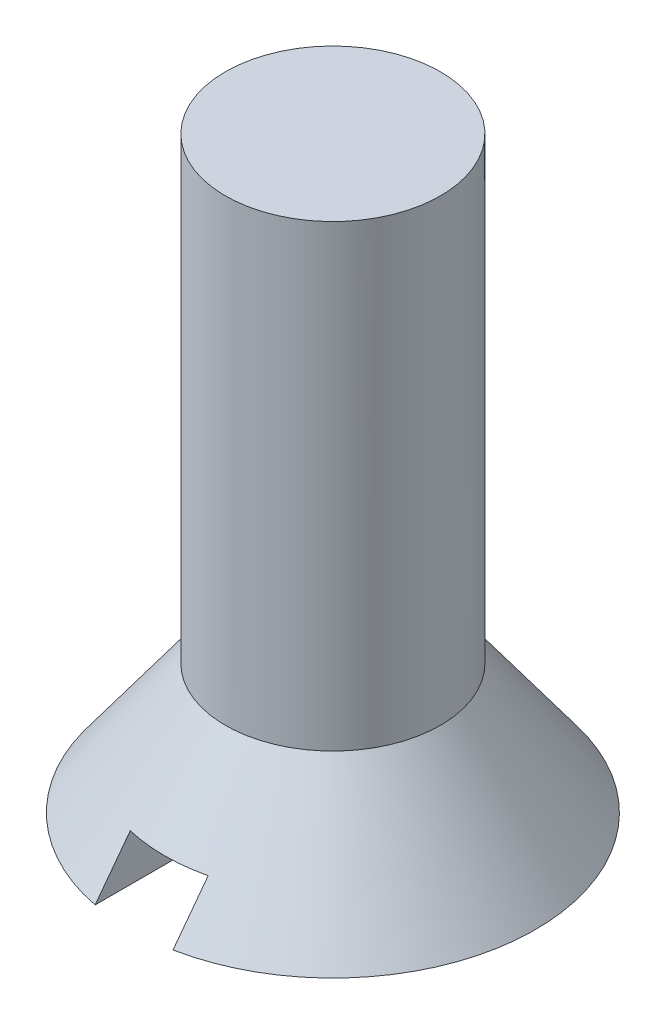
SolidWorks part; units mm, degrees
ref_plane "Front Plane" through (0, 0, 0) normal (0, 0, 1) x (1, 0, 0)
ref_plane "Top Plane" through (0, 0, 0) normal (0, 1, 0) x (1, 0, 0)
ref_plane "Right Plane" through (0, 0, 0) normal (1, 0, 0) x (0, 0, -1)
sketch "Sketch1" plane through (0, 0, 0) normal (0, 1, 0) x (1, 0, 0)
  circle A0 centre (0, 0) radius 3.302
  dimension "D1" = 6.604
sketch "Sketch2" plane through (0, 0, 0) normal (0, 0, 1) x (1, 0, 0)
  line L0 (3.302, 0) -> (-3.302, 0) construction
  line L1 (3.302, 0) -> (0, 0)
  line L4 (0, 2.1082) -> (1.7526, 2.1082)
  line L5 (1.7526, 2.1082) -> (3.302, 0)
  line L6 (0, 2.1082) -> (0, 0)
  point P2 (0, 0)
  dimension "D1" = 2.1082
  dimension "D3" = 1.7526
revolve "Revolve2" add sketch "Sketch2" angle 360 about L6
sketch "Sketch3" plane through (0, 2.1082, 0) normal (0, 1, 0) x (-1, 0, 0)
  circle A0 centre (0, 0) radius 1.7526
extrude "Boss-Extrude1" add sketch "Sketch3" along normal blind 7.474
sketch "Sketch4" plane through (0, 0, 0) normal (0, 0, 1) x (1, 0, 0)
  line L0 (0, 0) -> (0.635, 0)
  line L1 (3.302, 0) -> (-3.302, 0) construction
  line L2 (0.635, 0) -> (0.635, 0.762)
  line L3 (0.635, 0.762) -> (0.1238, 0.762)
  line L4 (0.1238, 0.762) -> (-0.635, 0.762)
  line L5 (-0.635, 0.762) -> (-0.635, 0)
  line L6 (-0.635, 0) -> (0, 0)
  dimension "D1" = 1.27
  dimension "D2" = 0.635
  dimension "D3" = 0.635
  dimension "D4" = 0.762
extrude "Cut-Extrude1" cut sketch "Sketch4" along normal blind 4.1148 and the other way blind 4.572
